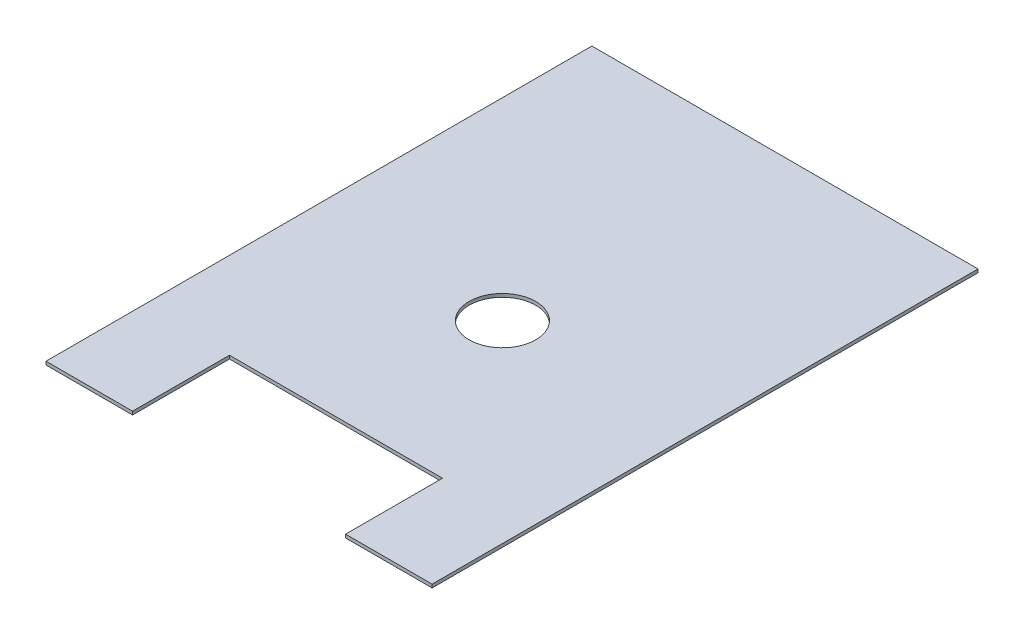
SolidWorks part; units mm, degrees
material "6061-T6 (SS)"
ref_plane "Front Plane" through (0, 0, 0) normal (0, 0, 1) x (1, 0, 0)
ref_plane "Top Plane" through (0, 0, 0) normal (0, 1, 0) x (1, 0, 0)
ref_plane "Right Plane" through (0, 0, 0) normal (1, 0, 0) x (0, 0, -1)
sketch "Sketch1" plane through (0, 0, 0) normal (0, 1, 0) x (1, 0, 0)
  line L1 (-184.15, -260.35) -> (184.15, -260.35)
  line L2 (-184.15, -260.35) -> (-184.15, 260.35)
  line L3 (-184.15, 260.35) -> (184.15, 260.35)
  line L4 (184.15, -260.35) -> (184.15, 260.35)
  line L5 (-184.15, -260.35) -> (184.15, 260.35) construction
  line L6 (-184.15, 260.35) -> (184.15, -260.35) construction
  point P0 (0, 0)
  dimension "D1" = 520.7
  dimension "D2" = 368.3
base flange "Base-Flange1" sketch "Sketch1" thickness 3.175 reverse thickness direction no parameters "D1"=0.7366
sketch "Sketch6" plane through (0, 0, 0) normal (0, 1, 0) x (1, 0, 0)
  line L0 (0, 0) -> (0, -260.35) construction
  line L1 (-184.15, -260.35) -> (184.15, -260.35) construction
  line L3 (-101.6, -352.806) -> (101.6, -352.806)
  line L4 (-101.6, -352.806) -> (-101.6, -167.894)
  line L5 (-101.6, -167.894) -> (101.6, -167.894)
  line L6 (101.6, -352.806) -> (101.6, -167.894)
  line L7 (-101.6, -352.806) -> (101.6, -167.894) construction
  line L8 (-101.6, -167.894) -> (101.6, -352.806) construction
  dimension "D1" = 184.912
  dimension "D2" = 203.2
extrude "Cut-Extrude1" cut sketch "Sketch6" against normal through all normal cut yes
sketch "Sketch7" plane through (0, 0, 0) normal (0, 1, 0) x (1, 0, 0)
  line L0 (0, -167.894) -> (0, -9.144) construction
  line L1 (101.6, -167.894) -> (-101.6, -167.894) construction
  circle A0 centre (0, -9.144) radius 31.75
  dimension "D2" = 63.5
  dimension "D1" = 158.75
extrude "Cut-Extrude2" cut sketch "Sketch7" against normal through all normal cut yes
sketch "Bend-Lines1" [suppressed] plane through (0, 0, 0) normal (0, 1, 0) x (1, 0, 0)
sketch "Bounding-Box1" [suppressed] plane through (0, 0, 0) normal (0, 1, 0) x (1, 0, 0)
sheet metal parameters "Sheet-Metal1" thickness 3.175 parameters "D1"=0.7366
flat pattern "Flat-Pattern1" [suppressed]
sketch "Bend-Lines2" plane through (0, 0, 0) normal (0, 1, 0) x (1, 0, 0)
sketch3d "Bounding-Box2" [suppressed]
  line L0 (190.5, -260.35, 0) -> (190.5, 260.35, 0) construction
  line L1 (-190.5, -260.35, 0) -> (-190.5, 260.35, 0) construction
  line L2 (190.5, -260.35, 0) -> (-190.5, -260.35, 0) construction
  line L3 (190.5, 260.35, 0) -> (-190.5, 260.35, 0) construction
sheet metal parameters "Sheet-Metal2" thickness 3.175 parameters "D1"=0.7366
flat pattern "Flat-Pattern1"
sketch "Bend-Lines2" plane through (0, 0, 0) normal (0, 1, 0) x (1, 0, 0)
sketch3d "Bounding-Box2" [suppressed]
  line L0 (-190.5, -260.35, 0) -> (-190.5, 260.35, 0) construction
  line L1 (190.5, -260.35, 0) -> (190.5, 260.35, 0) construction
  line L2 (-190.5, -260.35, 0) -> (190.5, -260.35, 0) construction
  line L3 (-190.5, 260.35, 0) -> (190.5, 260.35, 0) construction
sheet metal parameters "Sheet-Metal3" thickness 3.175 parameters "D1"=0.7366
flat pattern "Flat-Pattern1"
sketch "Bend-Lines2" plane through (0, -123.5327, 21.7822) normal (0, -0.9848, 0.1736) x (-1, 0, 0)
sketch3d "Bounding-Box2" [suppressed]
  line L0 (-184.15, -260.35, 0) -> (-184.15, 260.35, 0) construction
  line L1 (184.15, -260.35, 0) -> (184.15, 260.35, 0) construction
  line L2 (-184.15, -260.35, 0) -> (184.15, -260.35, 0) construction
  line L3 (-184.15, 260.35, 0) -> (184.15, 260.35, 0) construction
